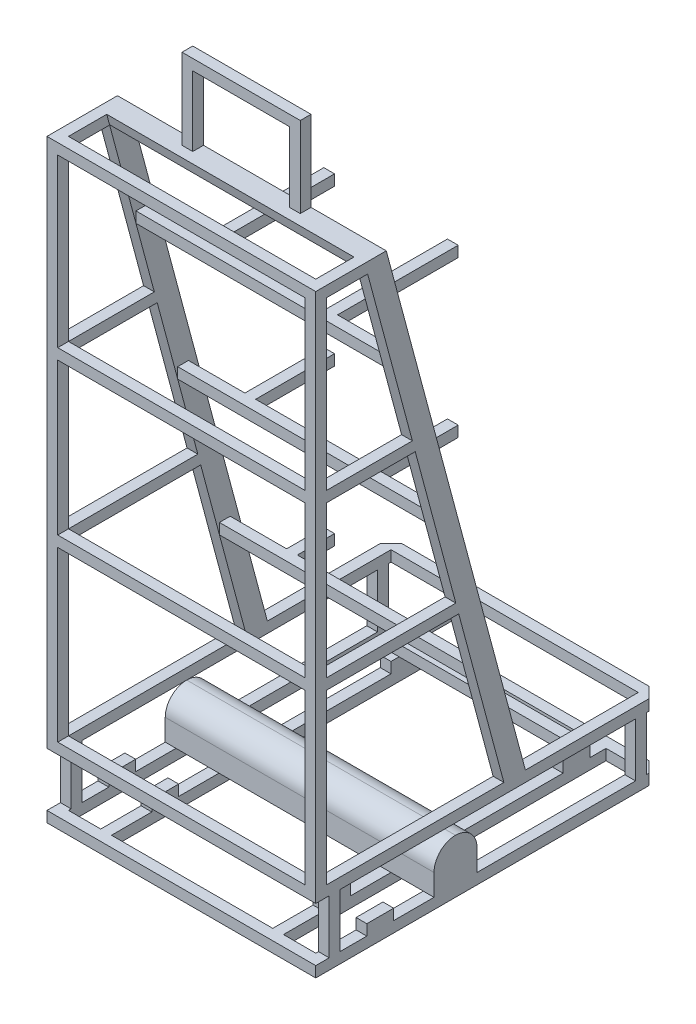
SolidWorks part; units mm, degrees
ref_plane "Front Plane" through (0, 0, 0) normal (0, 0, 1) x (1, 0, 0)
ref_plane "Top Plane" through (0, 0, 0) normal (0, 1, 0) x (1, 0, 0)
ref_plane "Right Plane" through (0, 0, 0) normal (1, 0, 0) x (0, 0, -1)
sketch "Sketch1" plane through (0, 0, 0) normal (0, 1, 0) x (1, 0, 0)
  line L5 (53.019, 69.062) -> (553.019, 69.062)
  line L6 (53.019, 69.062) -> (53.019, -570.938)
  line L7 (53.019, -570.938) -> (553.019, -570.938)
  line L8 (553.019, 69.062) -> (553.019, -570.938)
  line L9 (533.019, -250.938) -> (533.019, 49.062)
  line L10 (533.019, 49.062) -> (73.019, 49.062)
  line L11 (73.019, 49.062) -> (73.019, -550.938)
  line L12 (73.019, -550.938) -> (533.019, -550.938)
  line L13 (533.019, -550.938) -> (533.019, -250.938)
  dimension "D1" = 500
extrude "Boss-Extrude1" add sketch "Sketch1" along normal blind 20
sketch "Sketch2" plane through (0, 20, 0) normal (0, 1, 0) x (1, 0, 0)
  line L3 (553.019, -545.938) -> (533.019, -545.938)
  line L4 (553.019, -545.938) -> (553.019, -525.938)
  line L5 (553.019, -525.938) -> (533.019, -525.938)
  line L6 (533.019, -545.938) -> (533.019, -525.938)
  line L12 (553.019, 24.062) -> (533.019, 24.062)
  line L13 (533.019, 44.062) -> (533.019, 24.062)
  line L14 (553.019, 44.062) -> (533.019, 44.062)
  line L15 (553.019, 44.062) -> (553.019, 24.062)
  line L16 (53.019, -525.938) -> (73.019, -525.938)
  line L17 (73.019, -545.938) -> (73.019, -525.938)
  line L18 (53.019, -545.938) -> (73.019, -545.938)
  line L19 (53.019, -545.938) -> (53.019, -525.938)
  line L20 (53.019, 44.062) -> (53.019, 24.062)
  line L21 (53.019, 44.062) -> (73.019, 44.062)
  line L22 (73.019, 44.062) -> (73.019, 24.062)
  line L23 (53.019, 24.062) -> (73.019, 24.062)
extrude "Boss-Extrude5" add sketch "Sketch2" along normal blind 100
sketch "Sketch4" plane through (0, 120, 0) normal (0, 1, 0) x (1, 0, 0)
  line L0 (73.019, 49.062) -> (533.019, 49.062)
  line L1 (53.019, 69.062) -> (553.019, 69.062)
  line L2 (553.019, 69.062) -> (553.019, -570.938)
  line L3 (553.019, -570.938) -> (53.019, -570.938)
  line L4 (53.019, -570.938) -> (53.019, 69.062)
  line L5 (533.019, 49.062) -> (533.019, -550.938)
  line L6 (533.019, -550.938) -> (73.019, -550.938)
  line L7 (73.019, -550.938) -> (73.019, 49.062)
extrude "Boss-Extrude6" add sketch "Sketch4" along normal blind 20
sketch "Sketch5" plane through (0, 140, 0) normal (0, 1, 0) x (1, 0, 0)
  line L3 (553.019, -220.938) -> (533.019, -220.938)
  line L4 (553.019, -220.938) -> (553.019, -180.938)
  line L5 (553.019, -180.938) -> (533.019, -180.938)
  line L6 (533.019, -220.938) -> (533.019, -180.938)
  line L10 (53.019, -180.938) -> (73.019, -180.938)
  line L11 (73.019, -220.938) -> (73.019, -180.938)
  line L12 (53.019, -220.938) -> (73.019, -220.938)
  line L13 (53.019, -220.938) -> (53.019, -180.938)
sketch "Sketch10" plane through (0, 140, 0) normal (0, 1, 0) x (1, 0, 0)
  line L0 (53.019, -220.938) -> (553.019, -220.938)
ref_axis "Axis4" through (53.019, 140, 220.938) along (1, 0, 0)
ref_plane "Plane3" through (0, -45.8563, 171.1379) normal (0, -0.2588, 0.9659) x (1, 0, 0)
ref_plane "Plane5" through (0, 185.8563, 49.8) normal (0, -0.9659, -0.2588) x (1, 0, 0)
extrude "Boss-Extrude10" add sketch "Sketch5" along direction (0, -0.9659, -0.2588) on the side of the normal blind 1000
sketch "Sketch13" plane through (73.019, 0, 0) normal (1, 0, 0) x (0, 0, -1)
  line L0 (-479.757, 1105.9258) -> (-439.757, 1105.9258)
  line L1 (-439.757, 1105.9258) -> (-434.5806, 1086.6073)
  line L3 (-434.5806, 1086.6073) -> (-474.5806, 1086.6073)
  line L5 (-474.5806, 1086.6073) -> (-479.757, 1105.9258)
extrude "Boss-Extrude11" add sketch "Sketch13" along normal blind 460 contours L5 L0 L1 L3
sketch "Sketch14" plane through (0, 1105.9258, 0) normal (0, 1, 0) x (1, 0, 0)
  line L1 (193.019, -439.757) -> (213.019, -439.757)
  line L7 (213.019, -439.757) -> (213.019, -459.757)
  line L8 (213.019, -459.757) -> (193.019, -459.757)
  line L9 (193.019, -459.757) -> (193.019, -439.757)
extrude "Boss-Extrude12" add sketch "Sketch14" along normal blind 150 contours L1 L7 L8 L9
sketch "Sketch15" plane through (0, 1105.9258, 0) normal (0, 1, 0) x (1, 0, 0)
  line L2 (413.019, -439.757) -> (413.019, -459.757)
  line L3 (413.019, -459.757) -> (393.019, -459.757)
  line L4 (393.019, -459.757) -> (393.019, -439.757)
  line L5 (393.019, -439.757) -> (413.019, -439.757)
extrude "Boss-Extrude13" add sketch "Sketch15" along normal blind 150 contours L2 L3 L4 L5
sketch "Sketch16" plane through (213.019, 0, 0) normal (1, 0, 0) x (0, 0, -1)
  line L0 (-459.757, 1255.9258) -> (-439.757, 1255.9258)
  line L1 (-439.757, 1255.9258) -> (-439.757, 1235.9258)
  line L2 (-439.757, 1255.9258) -> (-439.757, 1105.9258) construction
  line L3 (-439.757, 1235.9258) -> (-459.757, 1235.9258)
  line L4 (-459.757, 1255.9258) -> (-459.757, 1105.9258) construction
  line L5 (-459.757, 1235.9258) -> (-459.757, 1255.9258)
extrude "Boss-Extrude14" add sketch "Sketch16" along normal blind 180 contours L5 L0 L1 L3
sketch "Sketch17" plane through (533.019, 0, 0) normal (-1, 0, 0) x (0, 0, 1)
  line L0 (425.405, 903.0814) -> (425.405, 923.0814)
  line L1 (425.405, 923.0814) -> (405.405, 923.0814)
  line L2 (405.405, 923.0814) -> (405.405, 903.0814)
  line L4 (405.405, 903.0814) -> (425.405, 903.0814)
extrude "Boss-Extrude16" add sketch "Sketch17" along normal blind 460 contours L0 L1 L2 L4
sketch "Sketch19" plane through (73.019, 0, 0) normal (1, 0, 0) x (0, 0, -1)
  line L0 (-425.405, 903.0814) -> (-347.7593, 613.3037)
  line L2 (-347.7593, 613.3037) -> (-327.7593, 613.3037)
  line L3 (-327.7593, 613.3037) -> (-327.7593, 633.3037)
  line L4 (-327.7593, 633.3037) -> (-347.7593, 633.3037)
  line L5 (-347.7593, 633.3037) -> (-347.7593, 613.3037)
extrude "Boss-Extrude17" add sketch "Sketch19" along normal blind 460 contours L2 L3 L4 L5
sketch "Sketch20" plane through (73.019, 0, 0) normal (1, 0, 0) x (0, 0, -1)
  line L0 (-347.7593, 613.3037) -> (-270.1136, 323.5259)
  line L2 (-270.1136, 323.5259) -> (-250.1136, 323.5259)
  line L3 (-250.1136, 323.5259) -> (-250.1136, 343.5259)
  line L4 (-250.1136, 343.5259) -> (-270.1136, 343.5259)
  line L5 (-270.1136, 343.5259) -> (-270.1136, 323.5259)
extrude "Boss-Extrude18" add sketch "Sketch20" along normal blind 460 contours L2 L3 L4 L5
sketch "Sketch22" plane through (0, 0, 550.938) normal (0, 0, -1) x (-1, 0, 0)
  line L0 (-133.019, 0) -> (-153.019, 0)
  line L2 (-453.019, 0) -> (-453.019, 20)
  line L4 (-453.019, 20) -> (-473.019, 20)
  line L5 (-473.019, 20) -> (-473.019, 0)
  line L6 (-473.019, 0) -> (-453.019, 0)
  line L8 (-133.019, 20) -> (-133.019, 0)
  line L9 (-153.019, 20) -> (-133.019, 20)
  line L10 (-153.019, 0) -> (-153.019, 20)
extrude "Boss-Extrude19" add sketch "Sketch22" along normal blind 600
sketch "Sketch23" plane through (0, 20, 0) normal (0, 1, 0) x (1, 0, 0)
  line L2 (473.019, 19.062) -> (453.019, 19.062)
  line L4 (453.019, 19.062) -> (453.019, -30.938)
  line L5 (453.019, -30.938) -> (473.019, -30.938)
  line L6 (473.019, -30.938) -> (473.019, 19.062)
  line L9 (133.019, -30.938) -> (133.019, 19.062)
  line L10 (153.019, -30.938) -> (133.019, -30.938)
  line L11 (153.019, 19.062) -> (153.019, -30.938)
  line L12 (133.019, 19.062) -> (153.019, 19.062)
extrude "Boss-Extrude20" add sketch "Sketch23" along normal blind 20
sketch "Sketch24" plane through (0, 40, 0) normal (0, 1, 0) x (1, 0, 0)
  line L2 (473.019, 4.062) -> (453.019, 4.062)
  line L4 (453.019, 4.062) -> (453.019, -15.938)
  line L5 (453.019, -15.938) -> (473.019, -15.938)
  line L6 (473.019, -15.938) -> (473.019, 4.062)
extrude "Boss-Extrude21" add sketch "Sketch24" along normal blind 20 contours L2 L4 L5 L6
sketch "Sketch25" plane through (453.019, 0, 0) normal (-1, 0, 0) x (0, 0, 1)
  line L1 (-4.062, 60) -> (15.938, 60)
  line L2 (-4.062, 60) -> (-4.062, 40)
  line L3 (-4.062, 40) -> (15.938, 40)
  line L4 (15.938, 60) -> (15.938, 40)
extrude "Boss-Extrude22" add sketch "Sketch25" along normal blind 320
sketch "Sketch26" plane through (0, 60, 0) normal (0, 1, 0) x (1, 0, 0)
  circle A0 centre (303.019, -5.938) radius 5
extrude "Cut-Extrude1" cut sketch "Sketch26" against normal blind 40
sketch "Sketch27" plane through (0, 20, 0) normal (0, 1, 0) x (1, 0, 0)
  line L0 (553.019, -425.938) -> (553.019, -475.938)
  line L2 (553.019, -425.938) -> (533.019, -425.938)
  line L4 (533.019, -425.938) -> (533.019, -475.938)
  line L5 (533.019, -475.938) -> (553.019, -475.938)
  line L8 (453.019, -425.938) -> (473.019, -425.938)
  line L9 (473.019, -425.938) -> (473.019, -475.938)
  line L10 (473.019, -475.938) -> (453.019, -475.938)
  line L11 (453.019, -425.938) -> (453.019, -475.938)
  line L13 (53.019, -425.938) -> (73.019, -425.938)
  line L14 (73.019, -425.938) -> (73.019, -475.938)
  line L15 (73.019, -475.938) -> (53.019, -475.938)
  line L16 (53.019, -425.938) -> (53.019, -475.938)
  line L17 (153.019, -425.938) -> (153.019, -475.938)
  line L18 (133.019, -475.938) -> (153.019, -475.938)
  line L19 (133.019, -425.938) -> (133.019, -475.938)
  line L20 (153.019, -425.938) -> (133.019, -425.938)
extrude "Boss-Extrude24" add sketch "Sketch27" along normal blind 20
sketch "Sketch28" plane through (0, 140, 0) normal (0, 1, 0) x (1, 0, 0)
  line L0 (73.019, -550.938) -> (53.019, -550.938)
  line L1 (53.019, -220.938) -> (53.019, -570.938) construction
  line L2 (53.019, -550.938) -> (53.019, -570.938)
  line L3 (53.019, -570.938) -> (73.019, -570.938)
  line L4 (53.019, -570.938) -> (553.019, -570.938) construction
  line L5 (73.019, -570.938) -> (73.019, -550.938)
  line L6 (533.019, -550.938) -> (533.019, -570.938)
  line L7 (533.019, -570.938) -> (553.019, -570.938)
  line L8 (553.019, -570.938) -> (553.019, -550.938)
  line L9 (553.019, -570.938) -> (553.019, -220.938) construction
  line L10 (553.019, -550.938) -> (533.019, -550.938)
extrude "Boss-Extrude25" add sketch "Sketch28" along normal up to surface (965.9258 mm away) up to face at (303.019, 1105.9258, 453.0904)
sketch "Sketch29" plane through (0, 0, 550.938) normal (0, 0, -1) x (-1, 0, 0)
  line L0 (-53.019, 1105.9258) -> (-53.019, 140) construction
  line L1 (-73.019, 1105.9258) -> (-53.019, 1105.9258)
  line L2 (-73.019, 1105.9258) -> (-73.019, 1085.9258)
  line L3 (-73.019, 1085.9258) -> (-53.019, 1085.9258)
  line L4 (-53.019, 1105.9258) -> (-53.019, 1085.9258)
  line L5 (-533.019, 1105.9258) -> (-533.019, 140) construction
  line L6 (-553.019, 1105.9258) -> (-533.019, 1105.9258)
  line L7 (-553.019, 1105.9258) -> (-553.019, 1085.9258)
  line L8 (-553.019, 1085.9258) -> (-533.019, 1085.9258)
  line L9 (-533.019, 1105.9258) -> (-533.019, 1085.9258)
extrude "Boss-Extrude26" add sketch "Sketch29" along normal up to surface (71.181 mm away)
sketch "Sketch30" plane through (73.019, 0, 0) normal (1, 0, 0) x (0, 0, -1)
  line L1 (-570.938, 1105.9258) -> (-550.938, 1105.9258)
  line L2 (-570.938, 1105.9258) -> (-570.938, 1085.9258)
  line L3 (-570.938, 1085.9258) -> (-550.938, 1085.9258)
  line L4 (-550.938, 1105.9258) -> (-550.938, 1085.9258)
extrude "Boss-Extrude27" add sketch "Sketch30" along normal up to surface (460 mm away) up to face at (533.019, 50, 350.938)
chamfer "Chamfer1" distance 20 angle 45 4 edges at (53.019, 10, -69.062) (53.019, 130, -69.062) (553.019, 10, -69.062) (553.019, 130, -69.062)
sketch "Sketch32" plane through (0, 0, 550.938) normal (0, 0, -1) x (-1, 0, 0)
  line L5 (-553.019, 453.6543) -> (-533.019, 473.6543) construction
  line L6 (-73.019, 755.5152) -> (-53.019, 755.5152)
  line L7 (-73.019, 755.5152) -> (-73.019, 775.5152)
  line L8 (-53.019, 755.5152) -> (-53.019, 775.5152)
  line L9 (-73.019, 775.5152) -> (-53.019, 775.5152)
  line L10 (-73.019, 755.5152) -> (-53.019, 775.5152) construction
  line L11 (-53.019, 755.5152) -> (-73.019, 775.5152) construction
  line L12 (-73.019, 453.6543) -> (-53.019, 453.6543)
  line L13 (-73.019, 453.6543) -> (-73.019, 473.6543)
  line L14 (-53.019, 453.6543) -> (-53.019, 473.6543)
  line L15 (-73.019, 473.6543) -> (-53.019, 473.6543)
  line L16 (-73.019, 453.6543) -> (-53.019, 473.6543) construction
  line L17 (-53.019, 453.6543) -> (-73.019, 473.6543) construction
  line L18 (-533.019, 453.6543) -> (-553.019, 473.6543) construction
  line L19 (-553.019, 755.5152) -> (-533.019, 775.5152) construction
  line L20 (-533.019, 755.5152) -> (-553.019, 775.5152) construction
  line L21 (-533.019, 473.6543) -> (-553.019, 473.6543)
  line L22 (-553.019, 453.6543) -> (-553.019, 473.6543)
  line L23 (-533.019, 453.6543) -> (-533.019, 473.6543)
  line L24 (-533.019, 453.6543) -> (-553.019, 453.6543)
  line L25 (-533.019, 775.5152) -> (-553.019, 775.5152)
  line L26 (-553.019, 755.5152) -> (-553.019, 775.5152)
  line L27 (-533.019, 755.5152) -> (-533.019, 775.5152)
  line L28 (-533.019, 755.5152) -> (-553.019, 755.5152)
  point P11 (-63.019, 765.5152)
  point P12 (-63.019, 463.6543)
  point P25 (-543.019, 463.6543)
  point P26 (-543.019, 765.5152)
extrude "Boss-Extrude28" add sketch "Sketch32" along normal up to surface (245.9566 mm away)
sketch "Sketch33" plane through (73.019, 0, 0) normal (1, 0, 0) x (0, 0, -1)
  line L0 (-570.938, 1085.9258) -> (-570.938, 140) construction
  line L1 (-550.938, 775.5152) -> (-570.938, 775.5152)
  line L2 (-550.938, 775.5152) -> (-550.938, 755.5152)
  line L3 (-550.938, 755.5152) -> (-570.938, 755.5152)
  line L4 (-570.938, 775.5152) -> (-570.938, 755.5152)
  line L6 (-550.938, 453.6543) -> (-570.938, 453.6543)
  line L7 (-550.938, 453.6543) -> (-550.938, 473.6543)
  line L8 (-550.938, 473.6543) -> (-570.938, 473.6543)
  line L9 (-570.938, 453.6543) -> (-570.938, 473.6543)
extrude "Boss-Extrude29" add sketch "Sketch33" along normal up to surface (460 mm away) up to face at (533.019, 494.7407, 363.625)
sketch "Sketch34" plane through (0, 0, 250.1136) normal (0, 0, -1) x (-1, 0, 0)
  line L0 (-303.019, 343.5259) -> (-303.019, 323.5259)
  line L1 (-533.019, 343.5259) -> (-73.019, 343.5259) construction
  line L2 (-533.019, 323.5259) -> (-73.019, 323.5259) construction
  line L3 (-178.019, 323.5259) -> (-198.019, 343.5259) construction
  line L4 (-178.019, 343.5259) -> (-198.019, 323.5259) construction
  line L5 (-198.019, 343.5259) -> (-198.019, 323.5259)
  line L6 (-428.019, 343.5259) -> (-408.019, 343.5259)
  line L7 (-428.019, 343.5259) -> (-428.019, 323.5259)
  line L8 (-428.019, 323.5259) -> (-408.019, 323.5259)
  line L9 (-408.019, 343.5259) -> (-408.019, 323.5259)
  line L10 (-428.019, 343.5259) -> (-408.019, 323.5259) construction
  line L11 (-428.019, 323.5259) -> (-408.019, 343.5259) construction
  line L12 (-178.019, 323.5259) -> (-198.019, 323.5259)
  line L13 (-178.019, 343.5259) -> (-178.019, 323.5259)
  line L14 (-178.019, 343.5259) -> (-198.019, 343.5259)
  point P10 (-418.019, 333.5259)
  point P16 (-188.019, 333.5259)
  line M7 (-73.019, 343.5259) -> (-533.019, 343.5259)
  line M9 (-533.019, 323.5259) -> (-73.019, 323.5259)
extrude "Boss-Extrude30" add sketch "Sketch34" along normal up to vertex (69.1756 mm away) contours L13 L5 M7 M9 | L9 L8 L7 L6 region at (188.019, 333.5259, 250.1136) up to point (543.019, 140, 180.938)
sketch "Sketch35" plane through (0, 0, 327.7593) normal (0, 0, -1) x (-1, 0, 0)
  line L2 (-533.019, 613.3037) -> (-73.019, 613.3037) construction
  line L3 (-178.019, 613.3037) -> (-198.019, 633.3037) construction
  line L5 (-178.019, 633.3037) -> (-198.019, 613.3037) construction
  line L6 (-428.019, 633.3037) -> (-408.019, 633.3037)
  line L7 (-428.019, 633.3037) -> (-428.019, 613.3037)
  line L8 (-428.019, 613.3037) -> (-408.019, 613.3037)
  line L9 (-408.019, 633.3037) -> (-408.019, 613.3037)
  line L10 (-428.019, 633.3037) -> (-408.019, 613.3037) construction
  line L11 (-428.019, 613.3037) -> (-408.019, 633.3037) construction
  line L12 (-198.019, 633.3037) -> (-198.019, 613.3037)
  line L13 (-178.019, 613.3037) -> (-198.019, 613.3037)
  line L14 (-178.019, 633.3037) -> (-178.019, 613.3037)
  line L15 (-178.019, 633.3037) -> (-198.019, 633.3037)
  point P10 (-418.019, 623.3037)
  point P20 (-188.019, 623.3037)
extrude "Boss-Extrude31" add sketch "Sketch35" along normal up to surface (146.8213 mm away) up to face at (418.019, 333.5259, 180.938)
sketch "Sketch36" plane through (0, 0, 405.405) normal (0, 0, -1) x (-1, 0, 0)
  line L2 (-73.019, 903.0814) -> (-533.019, 903.0814) construction
  line L3 (-178.019, 903.0814) -> (-198.019, 923.0814) construction
  line L4 (-178.019, 923.0814) -> (-198.019, 903.0814) construction
  line L5 (-198.019, 923.0814) -> (-198.019, 903.0814)
  line L6 (-428.019, 923.0814) -> (-408.019, 923.0814)
  line L7 (-428.019, 923.0814) -> (-428.019, 903.0814)
  line L8 (-428.019, 903.0814) -> (-408.019, 903.0814)
  line L9 (-408.019, 923.0814) -> (-408.019, 903.0814)
  line L10 (-428.019, 923.0814) -> (-408.019, 903.0814) construction
  line L11 (-428.019, 903.0814) -> (-408.019, 923.0814) construction
  line L12 (-178.019, 903.0814) -> (-198.019, 903.0814)
  line L13 (-178.019, 923.0814) -> (-178.019, 903.0814)
  line L14 (-178.019, 923.0814) -> (-198.019, 923.0814)
  point P10 (-418.019, 913.0814)
  point P16 (-188.019, 913.0814)
extrude "Boss-Extrude32" add sketch "Sketch36" along normal up to surface (224.467 mm away) up to face at (418.019, 623.3037, 180.938)
sketch "Sketch37" plane through (0, 20, 0) normal (0, 1, 0) x (1, 0, 0)
  line L0 (53.019, -310.938) -> (53.019, -350.938)
  line L2 (53.019, -270.938) -> (553.019, -270.938)
  line L4 (53.019, -310.938) -> (53.019, -270.938)
  line L5 (553.019, -425.938) -> (553.019, 24.062) construction
  line L6 (553.019, -270.938) -> (553.019, -350.938)
  line L8 (53.019, 24.062) -> (53.019, -425.938) construction
  line L9 (553.019, -350.938) -> (53.019, -350.938)
extrude "Boss-Extrude33" add sketch "Sketch37" along normal blind 80
fillet "Fillet1" radius 40 2 edges at (303.019, 100, 350.938) (303.019, 100, 270.938)
